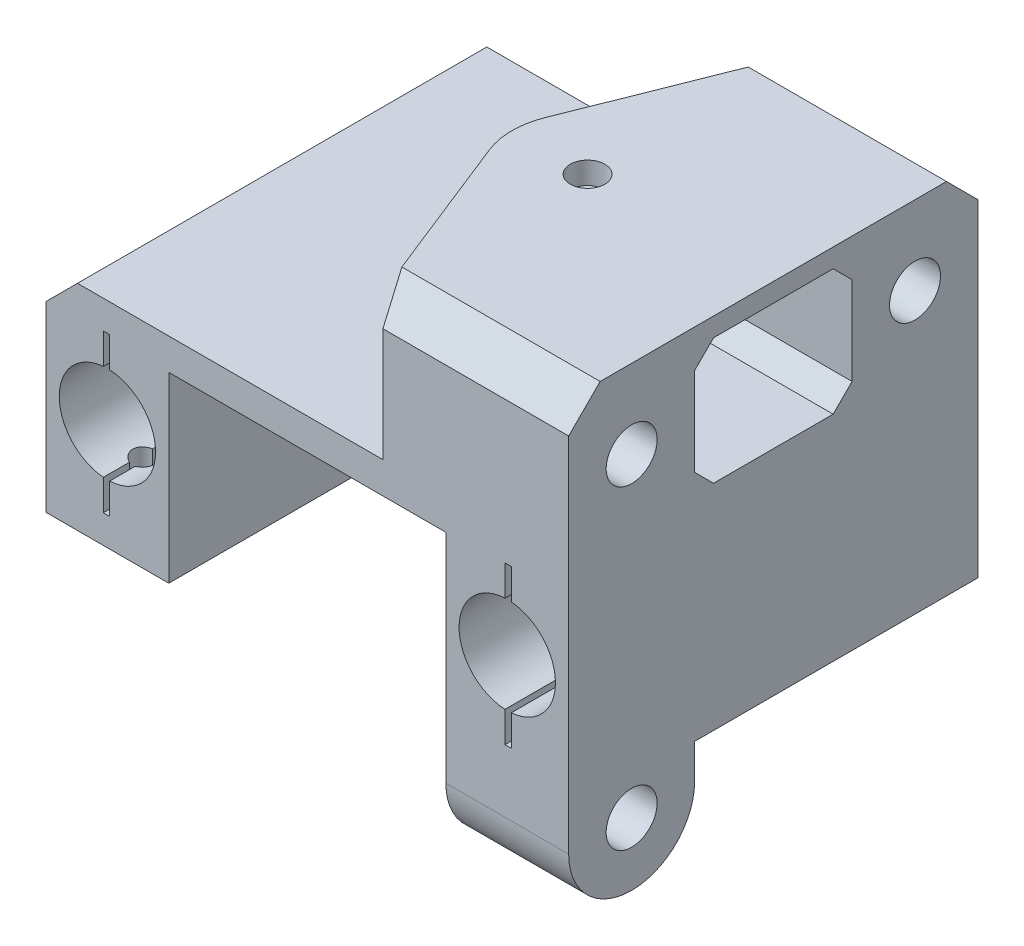
SolidWorks part; units mm, degrees
ref_plane "Front Plane" through (0, 0, 0) normal (0, 0, 1) x (1, 0, 0)
ref_plane "Top Plane" through (0, 0, 0) normal (0, 1, 0) x (1, 0, 0)
ref_plane "Right Plane" through (0, 0, 0) normal (1, 0, 0) x (0, 0, -1)
sketch "Sketch1" plane through (0, 0, 0) normal (0, 0, 1) x (1, 0, 0)
  line L0 (31.75, 17) -> (-31.75, 17)
  line L1 (-22, -12) -> (22, -12)
  line L2 (-22, -12) -> (-22, 12)
  line L3 (-22, 12) -> (22, 12)
  line L4 (22, -12) -> (22, 12)
  line L5 (-22, -12) -> (22, 12) construction
  line L6 (-22, 12) -> (22, -12) construction
  line L7 (-31.75, -17) -> (31.75, -17)
  line L8 (31.75, -17) -> (41.5, -17)
  line L9 (41.5, 17) -> (31.75, 17)
  line L10 (-31.75, -17) -> (-41.5, -17)
  line L11 (-41.5, -17) -> (-41.5, 17)
  line L12 (0, 0) -> (0, 8.5) construction
  line L13 (41.5, -17) -> (41.5, 17)
  line L15 (-41.5, 17) -> (-31.75, 17)
  circle A0 centre (-31.75, 0) radius 7.65
  circle A1 centre (31.75, 0) radius 7.65
  point P0 (0, 0)
  point P8 (-22, 0)
  point P12 (22, 0)
  dimension "D3" = 15.3
  dimension "D5" = 15.3
  dimension "D1" = 44
  dimension "D2" = 24
  dimension "D4" = 9.75
  dimension "D6" = 9.75
  dimension "D7" = 5
  dimension "D8" = 5
  dimension "D9" = 9.75
extrude "Boss-Extrude1" add sketch "Sketch1" along normal blind 65
sketch "Sketch6" plane through (0, 12, 0) normal (0, -1, 0) x (-1, 0, 0)
  line L0 (0, -65) -> (0, 0) construction
  line L1 (-22, -65) -> (22, -65) construction
  line L2 (-22, 0) -> (22, 0) construction
  circle A0 centre (-12, -32.5) radius 2.75
  point P9 (0, -32.5)
  dimension "D1" = 5.5
  dimension "D2" = 12
  dimension "D3" = 0
extrude "Cut-Extrude1" cut sketch "Sketch6" against normal blind 15
ref_plane "Plane2" through (0, 37, 0) normal (0, 1, 0) x (1, 0, 0)
sketch "Sketch7" plane through (41.5, 0, 0) normal (1, 0, 0) x (0, 0, -1)
  line L0 (-55, -22.5) -> (-10, -22.5) construction
  line L1 (-10, -22.5) -> (-10, 22.5) construction
  line L2 (-65, 17) -> (0, 17) construction
  line L3 (0, -17) -> (0, 17) construction
  line L4 (-65, -17) -> (-65, -22.5)
  line L5 (-45, -22.5) -> (-45, -17)
  line L6 (-65, -17) -> (0, -17) construction
  line L7 (-45, -17) -> (-65, -17)
  arc A0 (-65, -22.5) -> (-45, -22.5) centre (-55, -22.5) ccw
  circle A1 centre (-55, -22.5) radius 4.05
  point P1 (-32.5, -22.5)
  point P7 (-32.5, 17)
  point P8 (-10, 0)
  point P11 (0, 0)
  dimension "D2" = 8.1
  dimension "D3" = 0
  dimension "D1" = 45
  dimension "D4" = 0
extrude "Boss-Extrude2" add sketch "Sketch7" against normal up to surface (83 mm away) up to face at (-41.5, 0, 32.5)
sketch "Sketch8" plane through (0, 0, 0) normal (0, 0, -1) x (-1, 0, 0)
  line L0 (41.5, -17) -> (22, -17)
  line L1 (22, -12) -> (-22, -12) construction
  line L2 (-22, -12) -> (22, -12)
  line L3 (-22, -12) -> (-22, -37.9987)
  line L4 (-22, -37.9987) -> (22, -37.9987)
  line L5 (22, -12) -> (22, -17)
  line L6 (41.5, -17) -> (-41.5, -17) construction
  line L7 (41.5, -17) -> (41.5, -37.9987)
  line L8 (41.5, -37.9987) -> (22, -37.9987)
  point P6 (0, -12)
  dimension "D1" = 0
  dimension "D2" = 44
extrude "Cut-Extrude2" cut sketch "Sketch8" against normal blind 86
sketch "Sketch9" plane through (41.5, 0, 0) normal (-1, 0, 0) x (0, 0, 1)
  line L0 (0, 17) -> (0, 37)
  line L1 (0, 37) -> (20, 37)
  line L2 (20, 37) -> (20, 17)
  line L3 (65, 17) -> (0, 17) construction
  line L4 (20, 17) -> (0, 17)
  line L5 (10, 27.5) -> (0, 27.5) construction
  line L6 (10, 27.5) -> (20, 27.5) construction
  line L8 (65, 17) -> (45, 17)
  line L9 (65, 17) -> (65, 37)
  line L10 (65, 37) -> (45, 37)
  line L11 (45, 17) -> (45, 37)
  circle A0 centre (10, 27.5) radius 4.05
  circle A1 centre (55, -22.5) radius 4.05 construction
  circle A2 centre (55, 27.5) radius 4.05
  dimension "D1" = 8.1
  dimension "D2" = 50
  dimension "D3" = 45
  dimension "D4" = 20
extrude "Boss-Extrude3" add sketch "Sketch9" along normal up to surface (19.5 mm away) up to face at (22, -10.8333, 36.6667)
sketch "Sketch10" plane through (0, 12, 0) normal (0, -1, 0) x (-1, 0, 0)
  line L1 (-7.6699, -32.5) -> (-9.8349, -28.75)
  line L2 (-9.8349, -28.75) -> (-14.1651, -28.75)
  line L3 (-14.1651, -28.75) -> (-16.3301, -32.5)
  line L4 (-16.3301, -32.5) -> (-14.1651, -36.25)
  line L5 (-14.1651, -36.25) -> (-9.8349, -36.25)
  line L6 (-9.8349, -36.25) -> (-7.6699, -32.5)
  circle A0 centre (-12, -32.5) radius 3.75 construction
  dimension "D1" = 7.5
extrude "Cut-Extrude3" cut sketch "Sketch10" against normal blind 3.5
chamfer "Chamfer3" distance 3 angle 45 2 edges at (31.75, 17, 45) (31.75, 17, 20)
chamfer "Chamfer4" distance 5 angle 45 1 edges at (-41.5, 17, 32.5)
sketch "Sketch11" plane through (0, 37, 0) normal (0, 1, 0) x (1, 0, 0)
  line L0 (22, -65) -> (2.514, -39.8495)
  line L1 (41.5, -65) -> (22, -65)
  line L2 (41.5, -65) -> (41.5, 0)
  line L3 (41.5, 0) -> (0, 0)
  line L5 (2.514, -25.1505) -> (22, 0)
  arc A0 (2.514, -25.1505) -> (2.514, -39.8495) centre (12, -32.5) ccw
  circle A1 centre (12, -32.5) radius 2.75
  line M3 (22, -45) -> (22, -65)
  line M4 (22, -65) -> (41.5, -65)
  line M5 (41.5, -65) -> (41.5, -45)
  line M6 (41.5, -45) -> (22, -45)
  dimension "D1" = 5.5
extrude "Boss-Extrude4" add sketch "Sketch11" along normal blind 3 contours M6 M3 M4 M5 | L5 A0 L0 L2 L3 M3 M6 region at (31.75, 37, 55) region at (23.3909, 37, 27.1993)
sketch "Sketch13" plane through (0, 0, 65) normal (0, 0, 1) x (1, 0, 0)
  line L0 (-31.8914, 12.5) -> (-31.8914, -12.5)
  circle A0 centre (-31.75, 0) radius 7.65 construction
  dimension "D1" = 25
  dimension "D2" = 12.5
extrude "Cut-Extrude-Thin1" cut sketch "Sketch13" against normal blind 77 and the other way through all thin thin type mid plane wall 1
mirror "Mirror2" about plane through (0, 0, 0) normal (1, 0, 0) of "Cut-Extrude-Thin1"
chamfer "Chamfer5" distance 3 angle 45 2 edges at (31.75, 37, 20) (31.75, 37, 45)
sketch "Sketch14" plane through (0, 17, 0) normal (0, 1, 0) x (1, 0, 0)
  circle A0 centre (12, -32.5) radius 2.75
  circle A1 centre (12, -32.5) radius 3
  dimension "D1" = 6
extrude "Boss-Extrude5" add sketch "Sketch14" along normal blind 0.5
chamfer "Chamfer8" distance 0.5 angle 45 1 edges at (15, 17, 32.5)
sketch "Sketch15" plane through (0, 37, 0) normal (0, -1, 0) x (-1, 0, 0)
  circle A0 centre (-12, -32.5) radius 2.75
  circle A1 centre (-12, -32.5) radius 3
  dimension "D1" = 6
extrude "Boss-Extrude6" add sketch "Sketch15" along normal blind 0.5
chamfer "Chamfer9" distance 0.5 angle 45 1 edges at (12, 37, 35.5)
sketch "Sketch16" plane through (22, 0, 0) normal (-1, 0, 0) x (0, 0, 1)
  line L6 (0, 37) -> (0, 17)
  line L7 (0, 17) -> (23, 17)
  line L8 (23, 17) -> (20, 20)
  line L9 (20, 20) -> (20, 34)
  line L10 (20, 34) -> (23, 37)
  line L11 (23, 37) -> (0, 37)
  line L12 (0, 37) -> (0, 17)
  line L13 (0, 17) -> (23, 17)
  line L14 (23, 17) -> (20, 20)
  line L15 (20, 20) -> (20, 34)
  line L16 (20, 34) -> (23, 37)
  line L17 (23, 37) -> (0, 37)
  line L18 (42, 17) -> (65, 17)
  line L19 (65, 17) -> (65, 37)
  line L20 (65, 37) -> (42, 37)
  line L21 (42, 37) -> (45, 34)
  line L22 (45, 34) -> (45, 20)
  line L23 (45, 20) -> (42, 17)
  line L24 (42, 17) -> (65, 17)
  line L25 (65, 17) -> (65, 37)
  line L26 (65, 37) -> (42, 37)
  line L27 (42, 37) -> (45, 34)
  line L28 (45, 34) -> (45, 20)
  line L29 (45, 20) -> (42, 17)
  circle A0 centre (10, 27.5) radius 4.05
  circle A1 centre (55, 27.5) radius 4.05
  dimension "D1" = 0
  dimension "D2" = 0
extrude "Boss-Extrude7" add sketch "Sketch16" along normal blind 10
sketch "Sketch17" plane through (0, 37, 0) normal (0, 1, 0) x (1, 0, 0)
  line L0 (22, 0) -> (12, 0)
  line L1 (0.8479, -28.0692) -> (12, 0)
  line L2 (22, 0) -> (12, -20.5)
  arc A0 (12, -20.5) -> (0.8479, -28.0692) centre (12, -32.5) ccw
extrude "Boss-Extrude8" add sketch "Sketch17" along normal blind 3
sketch "Sketch18" plane through (0, -17, 0) normal (0, -1, 0) x (-1, 0, 0)
  line L0 (31.75, 0) -> (31.75, -65) construction
  line L1 (41.5, 0) -> (22, 0) construction
  line L2 (41.5, -65) -> (22, -65) construction
  line L3 (-31.75, 0) -> (-31.75, -40) construction
  line L4 (-22, 0) -> (-41.5, 0) construction
  circle A0 centre (31.75, -6) radius 1.95
  circle A1 centre (-31.75, -6) radius 1.95
  circle A2 centre (31.75, -59) radius 1.95
  circle A3 centre (-31.75, -32.5) radius 1.95
  point P20 (0, 0)
  dimension "D1" = 3.9
  dimension "D2" = 6
  dimension "D3" = 6
  dimension "D4" = 6
  dimension "D5" = 26.5
extrude "Cut-Extrude4" cut sketch "Sketch18" against normal blind 16
ref_plane "Plane3" through (0, 0, 32.5) normal (0, 0, 1) x (1, 0, 0)
mirror "Mirror3" about plane through (0, 0, 32.5) normal (0, 0, 1) of "Boss-Extrude8"
chamfer "Chamfer10" distance 5 angle 45 2 edges at (26.75, 40, 65) (26.75, 40, 0)
chamfer "Chamfer11" distance 2 angle 45 2 edges at (12, 37, 52.5) (12, 37, 12.5)
sketch "Sketch19" plane through (0, 0, 32.5) normal (0, 0, 1) x (1, 0, 0)
  line L0 (33.7, -7.3973) -> (29.8, -7.3973)
  line L1 (32.3914, 7.6231) -> (31.3914, 7.6416)
  arc A0 (31.3914, 7.6416) -> (29.8, -7.3973) centre (31.75, 0) ccw
  arc A1 (31.3914, 7.6416) -> (29.8, -7.3973) centre (31.75, 0) ccw
  arc A2 (33.7, -7.3973) -> (32.3914, 7.6231) centre (31.75, 0) ccw
  arc A3 (33.7, -7.3973) -> (32.3914, 7.6231) centre (31.75, 0) ccw
  circle A4 centre (31.75, 0) radius 5
  dimension "D1" = 10
extrude "Boss-Extrude9" add sketch "Sketch19" along normal offset from surface 24 and the other way offset from surface 24 up to face at (-1.1364, 5.5455, 65) other way up to face at (-1.1364, 6.5455, 0)
mirror "Mirror4" about plane through (0, 0, 0) normal (1, 0, 0) of "Boss-Extrude9"
